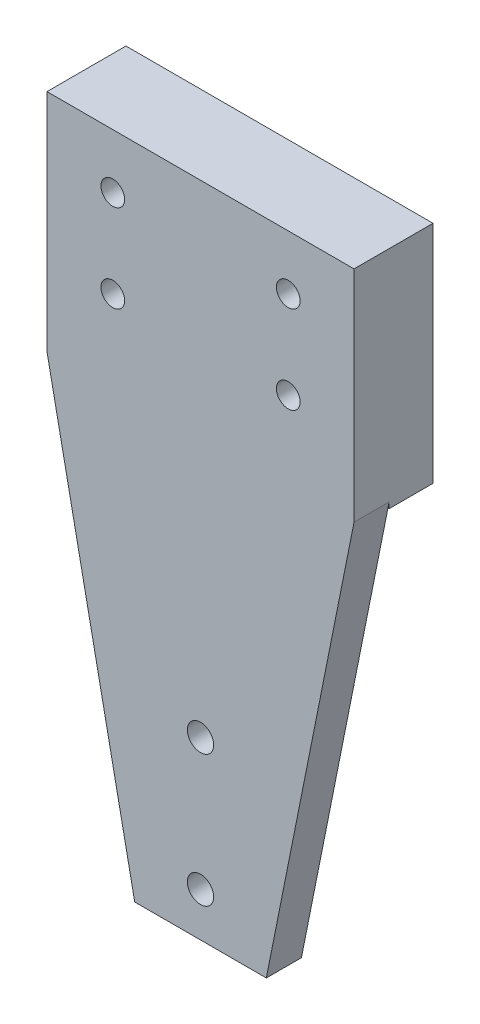
SolidWorks part; units mm, degrees
ref_plane "Front Plane" through (0, 0, 0) normal (0, 0, 1) x (1, 0, 0)
ref_plane "Top Plane" through (0, 0, 0) normal (0, 1, 0) x (1, 0, 0)
ref_plane "Right Plane" through (0, 0, 0) normal (1, 0, 0) x (0, 0, -1)
sketch "Sketch1" plane through (0, 0, 0) normal (0, 0, 1) x (1, 0, 0)
  line L0 (0, 0) -> (38.1, 0)
  line L1 (38.1, 0) -> (63.5, 127)
  line L2 (63.5, 127) -> (63.5, 190.5)
  line L3 (63.5, 190.5) -> (-25.4, 190.5)
  line L4 (-25.4, 190.5) -> (-25.4, 125.2916)
  line L5 (-25.4, 125.2916) -> (0, 0)
  line L6 (-12.7, 190.5) -> (12.7, 190.5)
  circle A0 centre (19.05, 12.7) radius 3.81
  circle A1 centre (19.05, 50.8) radius 3.81
  circle A2 centre (-6.35, 174.6877) radius 3.429
  circle A3 centre (-6.35, 149.2877) radius 3.429
  circle A4 centre (44.45, 149.2877) radius 3.429
  circle A5 centre (44.45, 174.6877) radius 3.429
  point P4 (19.05, 0)
  point P8 (19.05, 190.5)
  dimension "D5" = 7.62
  dimension "D9" = 7.62
  dimension "D11" = 6.858
  dimension "D13" = 19.05
  dimension "D1" = 63.5
  dimension "D2" = 88.9
  dimension "D3" = 38.1
  dimension "D4" = 190.5
  dimension "D6" = 12.7
  dimension "D7" = 19.05
  dimension "D8" = 38.1
  dimension "D10" = 19.05
  dimension "D12" = 25.4
extrude "Boss-Extrude1" add sketch "Sketch1" along normal blind 10.16 contours L5 L0 L1 L2 L3 L4 | A2 | A3 | A5 | A4 | A1 | A0
sketch "Sketch2" plane through (0, 0, 0) normal (0, 0, -1) x (-1, 0, 0)
  line L1 (-63.5, 190.5) -> (25.4, 190.5)
  line L2 (-63.5, 190.5) -> (-63.5, 125.2916)
  line L3 (-63.5, 125.2916) -> (25.4, 125.2916)
  line L4 (25.4, 190.5) -> (25.4, 125.2916)
extrude "Boss-Extrude2" add sketch "Sketch2" along normal blind 12.7
extrude "Cut-Extrude1" cut sketch "Sketch1<3>" along normal blind 12.7 from surface contours A2 | A5 | A4 | A3 starting at face at (19.05, 157.8958, -12.7)
sketch "Sketch1<3>" plane through (0, 0, 0) normal (0, 0, 1) x (1, 0, 0) same geometry as "Sketch1"
